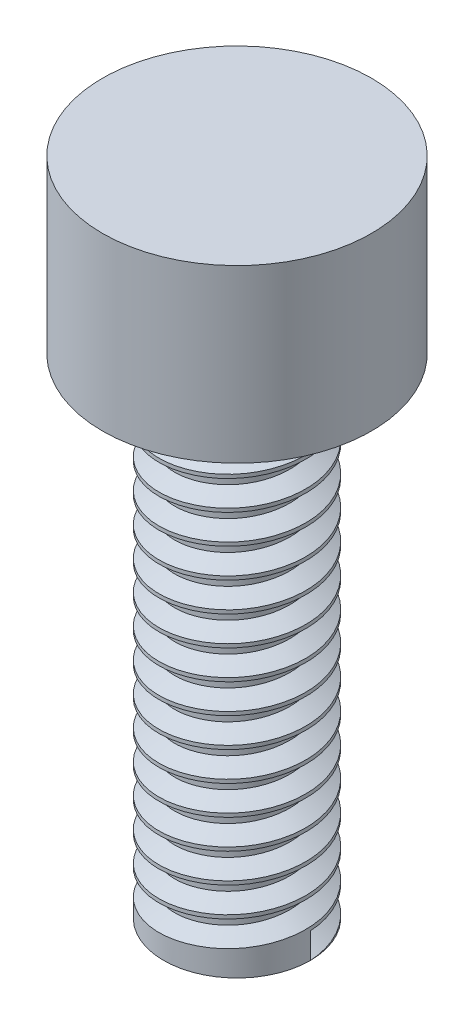
SolidWorks part; units mm, degrees
ref_plane "Front Plane" through (0, 0, 0) normal (0, 0, 1) x (1, 0, 0)
ref_plane "Top Plane" through (0, 0, 0) normal (0, 1, 0) x (1, 0, 0)
ref_plane "Right Plane" through (0, 0, 0) normal (1, 0, 0) x (0, 0, -1)
sketch "Sketch1" plane through (0, 0, 0) normal (0, 1, 0) x (1, 0, 0)
  circle A0 centre (0, 0) radius 1.5
  dimension "D1" = 3
extrude "Boss-Extrude1" add sketch "Sketch1" along normal blind 10
sketch "Sketch2" plane through (0, 10, 0) normal (0, 1, 0) x (1, 0, 0)
  circle A0 centre (0, 0) radius 2.75
  dimension "D1" = 5.5
extrude "Boss-Extrude2" add sketch "Sketch2" along normal blind 3.5
thread "Thread1" pitch 0.6 method cut profile "Thread Profile2" start angle 0, offset 0, length 10, pitch 0.6, diameter 3
ref_plane "Plane2" through (1.5, 0, 0) normal (0, 0, 1) x (1, 0, 0)
sketch "Thread Profile2" plane through (1.5, 0, 0) normal (0, 0, 1) x (1, 0, 0)
  line L0 (0, 0) -> (0, 0.6) construction
  line L11 (0, 0) -> (0, 0.525)
  line L12 (0, 0.525) -> (-0.3248, 0.3375)
  line L13 (-0.3248, 0.3375) -> (-0.3248, 0.1875)
  line L15 (-0.3248, 0.1875) -> (0, 0)
  line L17 (-0.3248, 0.2625) -> (0, 0.2625) construction
  point P2 (0, 0)
  dimension "Pitch" = 0.6
  dimension "Profile_Angle" = 60
  dimension "Profile_Land" = 0.15
  dimension "Profile_Height" = 0.3248
